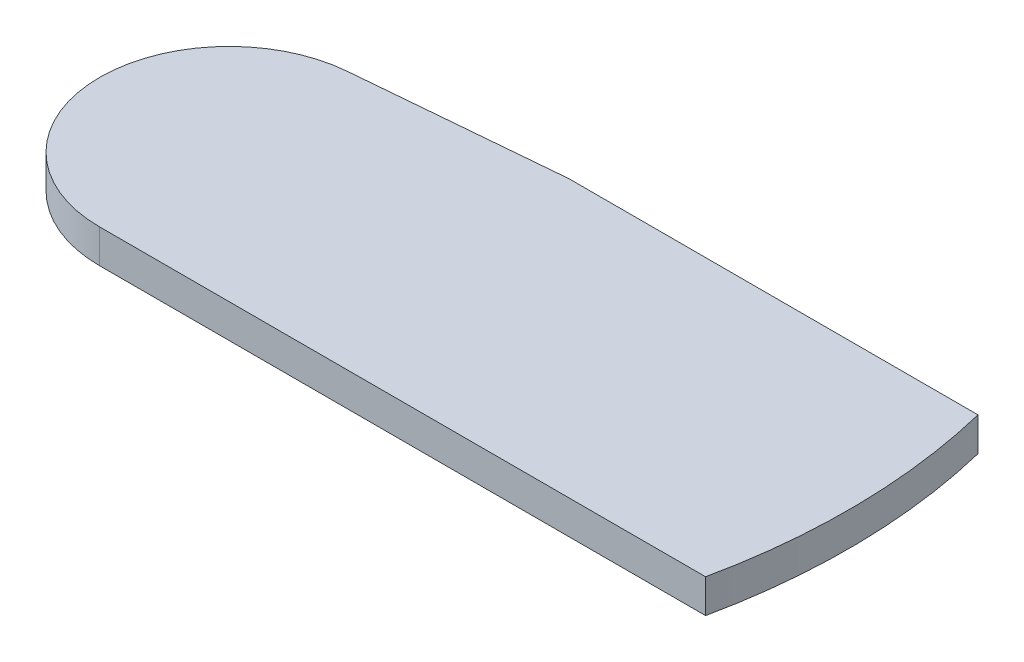
SolidWorks part; units mm, degrees
ref_plane "Płaszczyzna przednia" through (0, 0, 0) normal (0, 0, 1) x (1, 0, 0)
ref_plane "Płaszczyzna górna" through (0, 0, 0) normal (0, 1, 0) x (1, 0, 0)
ref_plane "Płaszczyzna prawa" through (0, 0, 0) normal (1, 0, 0) x (0, 0, -1)
sketch "Sketch1" plane through (0, 0, 0) normal (0, 1, 0) x (1, 0, 0)
  line L0 (-110.7065, 0) -> (22.5357, 0) construction
  line L1 (0, -110.7065) -> (0, 5424.6164) construction
  line L2 (-45.3355, 9.9619) -> (-29.5652, 11.3431)
  line L3 (-29.5652, 11.3431) -> (2.0157, 11.3431)
  line L4 (-29.5652, 11.3431) -> (-29.5652, -10)
  line L5 (-29.5652, -10) -> (2.3231, -10)
  line L7 (-44.463, -10) -> (-29.5652, -10)
  circle A0 centre (-44.463, 0) radius 10
  arc A1 (2.3231, -10) -> (2.0157, 11.3431) centre (-44.463, 0) ccw
  arc A2 (2.5566, -11.2335) -> (-9.8524, 33.7512) centre (-44.463, 0) ccw construction
  dimension "D1" = 20
  dimension "D2" = 0.5
extrude "Boss-Extrude1" add sketch "Sketch1" along normal blind 2.6 contours A0 | A0 L7 L4 L2 | L5 A1 L3 L4 region at (-33.5252, 0, -0.7119) region at (-44.463, 0, 0) region at (-13.2929, 0, -0.6549)
